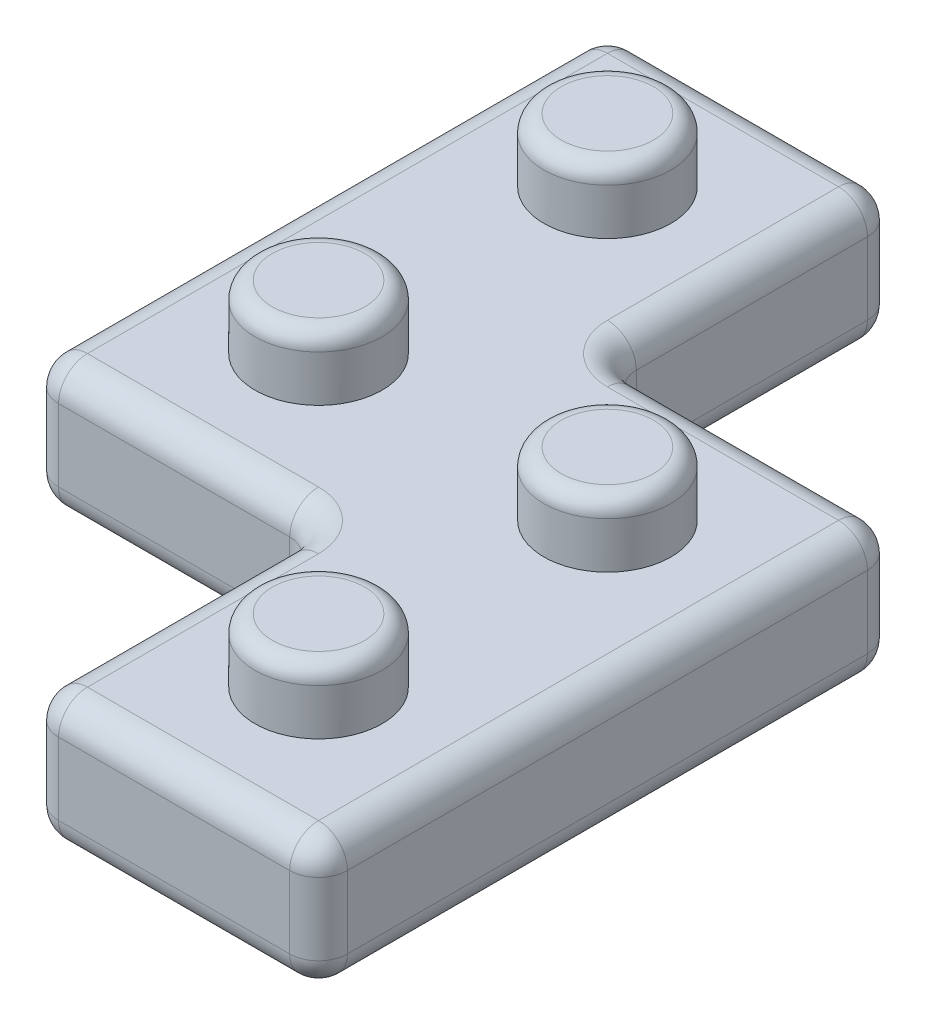
SolidWorks part; units mm, degrees
ref_plane "Front Plane" through (0, 0, 0) normal (0, 0, 1) x (1, 0, 0)
ref_plane "Top Plane" through (0, 0, 0) normal (0, 1, 0) x (1, 0, 0)
ref_plane "Right Plane" through (0, 0, 0) normal (1, 0, 0) x (0, 0, -1)
sketch "Sketch1" plane through (0, 0, 0) normal (0, 1, 0) x (1, 0, 0)
  line L0 (-11.43, 12.7) -> (-1.27, 12.7)
  line L1 (0, 11.43) -> (0, 1.27)
  line L2 (1.27, 0) -> (11.43, 0)
  line L3 (12.7, -1.27) -> (12.7, -24.13)
  line L4 (11.43, -25.4) -> (1.27, -25.4)
  line L5 (0, -24.13) -> (0, -13.97)
  line L6 (-1.27, -12.7) -> (-11.43, -12.7)
  line L7 (-12.7, -11.43) -> (-12.7, 11.43)
  arc A4 (-11.43, 12.7) -> (-12.7, 11.43) centre (-11.43, 11.43) ccw
  arc A5 (-11.43, -12.7) -> (-12.7, -11.43) centre (-11.43, -11.43) cw
  arc A6 (0, -13.97) -> (-1.27, -12.7) centre (-1.27, -13.97) ccw
  arc A7 (1.27, -25.4) -> (0, -24.13) centre (1.27, -24.13) cw
  arc A8 (12.7, -24.13) -> (11.43, -25.4) centre (11.43, -24.13) cw
  arc A9 (0, 1.27) -> (1.27, 0) centre (1.27, 1.27) ccw
  arc A10 (11.43, 0) -> (12.7, -1.27) centre (11.43, -1.27) cw
  arc A11 (-1.27, 12.7) -> (0, 11.43) centre (-1.27, 11.43) cw
  point P11 (-12.7, 12.7)
  point P14 (-12.7, -12.7)
  point P22 (0, -25.4)
  point P25 (12.7, -25.4)
  point P28 (0, 0)
  point P31 (12.7, 0)
  point P34 (0, 12.7)
  dimension "D6" = 1.27
  dimension "D1" = 12.7
  dimension "D2" = 12.7
  dimension "D3" = 25.4
  dimension "D4" = 12.7
  dimension "D5" = 25.4
extrude "Boss-Extrude1" add sketch "Sketch1" against normal blind 5.715 contours L7 A4 L0 A11 L1 A9 L2 A10 L3 A8 L4 A7 L5 A6 L6 A5
sketch "Sketch2" plane through (0, 0, 0) normal (0, 1, 0) x (1, 0, 0)
  line L0 (-11.43, 12.7) -> (-1.27, 12.7) construction
  line L1 (-12.7, -11.43) -> (-12.7, 11.43) construction
  circle A0 centre (-6.35, 6.35) radius 2.794
  circle A1 centre (-6.35, -6.35) radius 2.794
  circle A2 centre (6.35, -6.35) radius 2.794
  circle A3 centre (6.35, -19.05) radius 2.794
  dimension "D1" = 12.7
  dimension "D2" = 6.35
  dimension "D3" = 6.35
  dimension "D4" = 12.7
  dimension "D5" = 12.7
extrude "Boss-Extrude2" add sketch "Sketch2" along normal blind 2.794
fillet "Fillet4" radius 1.27 16 edges at (-6.35, 0, 12.7) (0, 0, 19.05) (6.35, 0, 25.4) (12.7, 0, 12.7) (6.35, 0, 0) (0, 0, -6.35) (-6.35, 0, -12.7) (-12.7, 0, 0) (-12.328, 0, 12.328) (-0.372, 0, 13.072) (0.372, 0, 25.028) (12.328, 0, 25.028) (12.328, 0, 0.372) (0.372, 0, -0.372) (-0.372, 0, -12.328) (-12.328, 0, -12.328)
fillet "Fillet5" radius 1.27 16 edges at (0, -5.715, -6.35) (6.35, -5.715, 0) (12.7, -5.715, 12.7) (6.35, -5.715, 25.4) (0, -5.715, 19.05) (-6.35, -5.715, 12.7) (-12.7, -5.715, 0) (-6.35, -5.715, -12.7) (-12.328, -5.715, -12.328) (-12.328, -5.715, 12.328) (-0.372, -5.715, 13.072) (0.372, -5.715, 25.028) (12.328, -5.715, 25.028) (12.328, -5.715, 0.372) (0.372, -5.715, -0.372) (-0.372, -5.715, -12.328)
fillet "Fillet7" radius 0.762 4 edges at (6.35, 2.794, 21.844) (6.35, 2.794, 9.144) (-6.35, 2.794, 9.144) (-6.35, 2.794, -3.556)
